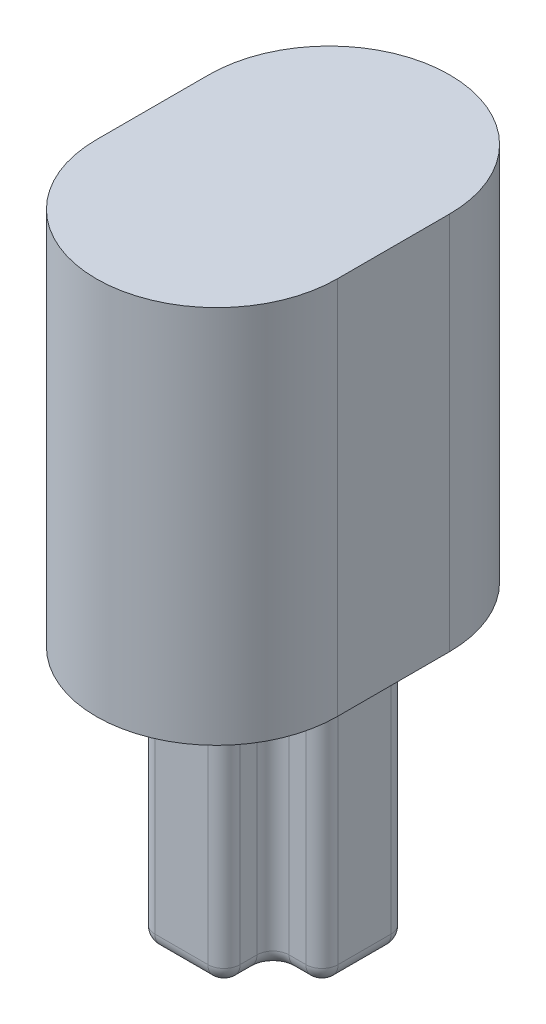
SolidWorks part; units mm, degrees
ref_plane "Front Plane" through (0, 0, 0) normal (0, 0, 1) x (1, 0, 0)
ref_plane "Top Plane" through (0, 0, 0) normal (0, 1, 0) x (1, 0, 0)
ref_plane "Right Plane" through (0, 0, 0) normal (1, 0, 0) x (0, 0, -1)
sketch "Sketch8" plane through (-2.2328, 0, 0.6657) normal (0, -1, 0) x (-1, 0, 0)
  line L0 (-26.6943, -20.8278) -> (-26.6943, -22.3528)
  line L9 (-28.2193, -19.5778) -> (-26.6943, -19.5778)
  line L10 (-28.2193, -19.5778) -> (-28.2193, -20.8278)
  line L11 (-28.2193, -20.8278) -> (-26.6943, -20.8278)
  line L12 (-23.9193, -19.5778) -> (-23.9193, -20.8278)
  line L13 (-28.2193, -19.5778) -> (-23.9193, -20.8278) construction
  line L14 (-28.2193, -20.8278) -> (-23.9193, -19.5778) construction
  line L15 (-26.6943, -18.0528) -> (-25.4443, -18.0528)
  line L16 (-26.6943, -18.0528) -> (-26.6943, -19.5778)
  line L17 (-26.6943, -22.3528) -> (-25.4443, -22.3528)
  line L18 (-25.4443, -18.0528) -> (-25.4443, -19.5778)
  line L19 (-26.6943, -18.0528) -> (-25.4443, -22.3528) construction
  line L20 (-26.6943, -22.3528) -> (-25.4443, -18.0528) construction
  line L21 (-25.4443, -20.8278) -> (-25.4443, -22.3528)
  line L22 (-25.4443, -19.5778) -> (-23.9193, -19.5778)
  line L23 (-25.4443, -20.8278) -> (-23.9193, -20.8278)
  line L25 (-24.7443, -18.8778) -> (-23.2193, -18.8778)
  line L26 (-23.2193, -18.8778) -> (-23.2193, -21.5278)
  line L27 (-24.7443, -21.5278) -> (-23.2193, -21.5278)
  line L28 (-24.7443, -21.5278) -> (-24.7443, -23.0528)
  line L29 (-27.3943, -23.0528) -> (-24.7443, -23.0528)
  line L30 (-27.3943, -21.5278) -> (-27.3943, -23.0528)
  line L31 (-28.9193, -21.5278) -> (-27.3943, -21.5278)
  line L32 (-28.9193, -18.8778) -> (-28.9193, -21.5278)
  line L33 (-28.9193, -18.8778) -> (-27.3943, -18.8778)
  line L34 (-27.3943, -17.3528) -> (-27.3943, -18.8778)
  line L35 (-27.3943, -17.3528) -> (-24.7443, -17.3528)
  line L36 (-24.7443, -17.3528) -> (-24.7443, -18.8778)
  point P0 (-26.0693, -20.2028)
  point P5 (-26.0693, -20.2028)
  point P10 (-26.0693, -20.2028)
  point P15 (0, 0)
  point P16 (-26.2796, -20.1943)
  point P17 (-26.0693, -20.2028)
  point P35 (4.0539, 0.4)
  point P37 (-23.2193, -20.2028)
  point P38 (-23.2193, -20.2028)
  dimension "D1" = 1.25
  dimension "D2" = 4.3
  dimension "D3" = 1.25
  dimension "D4" = 4.3
  dimension "D5" = 0.7
extrude "Boss-Extrude1" add sketch "Sketch8" along normal blind 8.1
sketch "Sketch9" plane through (0, 0, 0) normal (0, 1, 0) x (-1, 0, 0)
  line L0 (-23.8366, 22.6185) -> (-23.8366, 19.1185) construction
  line L1 (-20.0866, 22.6185) -> (-20.0866, 19.1185)
  line L2 (-27.5866, 22.6185) -> (-27.5866, 19.1185)
  line L3 (-25.1616, 22.1935) -> (-22.5116, 19.5435) construction
  line L15 (-22.5116, 18.0185) -> (-22.5116, 19.5435)
  line L16 (-22.5116, 19.5435) -> (-20.9866, 19.5435)
  line L17 (-20.9866, 19.5435) -> (-20.9866, 22.1935)
  line L18 (-20.9866, 22.1935) -> (-22.5116, 22.1935)
  line L19 (-22.5116, 22.1935) -> (-22.5116, 23.7185)
  line L20 (-22.5116, 23.7185) -> (-25.1616, 23.7185)
  line L21 (-25.1616, 23.7185) -> (-25.1616, 22.1935)
  line L22 (-25.1616, 22.1935) -> (-26.6866, 22.1935)
  line L23 (-26.6866, 22.1935) -> (-26.6866, 19.5435)
  line L24 (-26.6866, 19.5435) -> (-25.1616, 19.5435)
  line L25 (-25.1616, 19.5435) -> (-25.1616, 18.0185)
  line L26 (-25.1616, 18.0185) -> (-22.5116, 18.0185)
  line L27 (-22.5116, 18.0185) -> (-22.5116, 19.5435) construction
  line L28 (-22.5116, 19.5435) -> (-20.9866, 19.5435) construction
  line L29 (-20.9866, 19.5435) -> (-20.9866, 22.1935) construction
  line L30 (-20.9866, 22.1935) -> (-22.5116, 22.1935) construction
  line L31 (-22.5116, 22.1935) -> (-22.5116, 23.7185) construction
  line L32 (-22.5116, 23.7185) -> (-25.1616, 23.7185) construction
  line L33 (-25.1616, 23.7185) -> (-25.1616, 22.1935) construction
  line L34 (-25.1616, 22.1935) -> (-26.6866, 22.1935) construction
  line L35 (-26.6866, 22.1935) -> (-26.6866, 19.5435) construction
  line L36 (-26.6866, 19.5435) -> (-25.1616, 19.5435) construction
  line L37 (-25.1616, 19.5435) -> (-25.1616, 18.0185) construction
  line L38 (-25.1616, 18.0185) -> (-22.5116, 18.0185) construction
  arc A1 (-20.0866, 22.6185) -> (-27.5866, 22.6185) centre (-23.8366, 22.6185) ccw
  arc A2 (-27.5866, 19.1185) -> (-20.0866, 19.1185) centre (-23.8366, 19.1185) ccw
  point P5 (-23.8366, 20.8685)
  point P10 (-23.8366, 20.8685)
  dimension "D1" = 7.5
  dimension "D3" = 3.5
  dimension "D2" = 0
extrude "Boss-Extrude2" add sketch "Sketch9" along normal blind 11.8
fillet "Fillet1" radius 0.5 12 edges at (22.5116, -4.05, 19.5435) (20.9866, -4.05, 19.5435) (20.9866, -4.05, 22.1935) (22.5116, -4.05, 22.1935) (22.5116, -4.05, 23.7185) (25.1616, -4.05, 23.7185) (25.1616, -4.05, 22.1935) (26.6866, -4.05, 22.1935) (26.6866, -4.05, 19.5435) (25.1616, -4.05, 19.5435) (22.5116, -4.05, 18.0185) (25.1616, -4.05, 18.0185)
fillet "Fillet2" radius 0.5 24 edges at (22.5116, 0, 18.781) (22.658, 0, 18.1649) (23.8366, 0, 18.0185) (25.0151, 0, 18.1649) (25.1616, 0, 18.781) (25.308, 0, 19.397) (25.9241, 0, 19.5435) (26.5401, 0, 19.6899) (26.6866, 0, 20.8685) (26.5401, 0, 22.047) (25.9241, 0, 22.1935) (25.308, 0, 22.3399) (25.1616, 0, 22.956) (25.0151, 0, 23.572) (23.8366, 0, 23.7185) (22.658, 0, 23.572) (22.5116, 0, 22.956) (22.3651, 0, 22.3399) (21.7491, 0, 22.1935) (21.133, 0, 22.047) (20.9866, 0, 20.8685) (21.133, 0, 19.6899) (21.7491, 0, 19.5435) (22.3651, 0, 19.397)
fillet "Fillet4" radius 0.5 24 edges at (25.0151, -8.1, 23.572) (25.1616, -8.1, 22.956) (25.308, -8.1, 22.3399) (25.9241, -8.1, 22.1935) (26.5401, -8.1, 22.047) (26.6866, -8.1, 20.8685) (26.5401, -8.1, 19.6899) (25.9241, -8.1, 19.5435) (25.308, -8.1, 19.397) (25.1616, -8.1, 18.781) (25.0151, -8.1, 18.1649) (23.8366, -8.1, 18.0185) (22.658, -8.1, 18.1649) (22.5116, -8.1, 18.781) (22.3651, -8.1, 19.397) (21.7491, -8.1, 19.5435) (21.133, -8.1, 19.6899) (20.9866, -8.1, 20.8685) (21.133, -8.1, 22.047) (21.7491, -8.1, 22.1935) (22.3651, -8.1, 22.3399) (22.5116, -8.1, 22.956) (22.658, -8.1, 23.572) (23.8366, -8.1, 23.7185)
equation "\"baseLength\"= 18"
equation "\"firstLoftL\"= \"baseLength\" - 0.25"
equation "\"topSide\"= \"baseWidth\" - 3"
equation "\"topBtm\"= \"baseLength\" - 6"
equation "\"offset\"= 1"
equation "\"firstLoftH\"= 1.8"
equation "\"secLoftH\"= 9.5"
equation "\"baseWidth\"= 18"
equation "\"firstLoftW\"= \"baseWidth\" - 0.25"
equation "\"surfaceCurve\"= 60"
